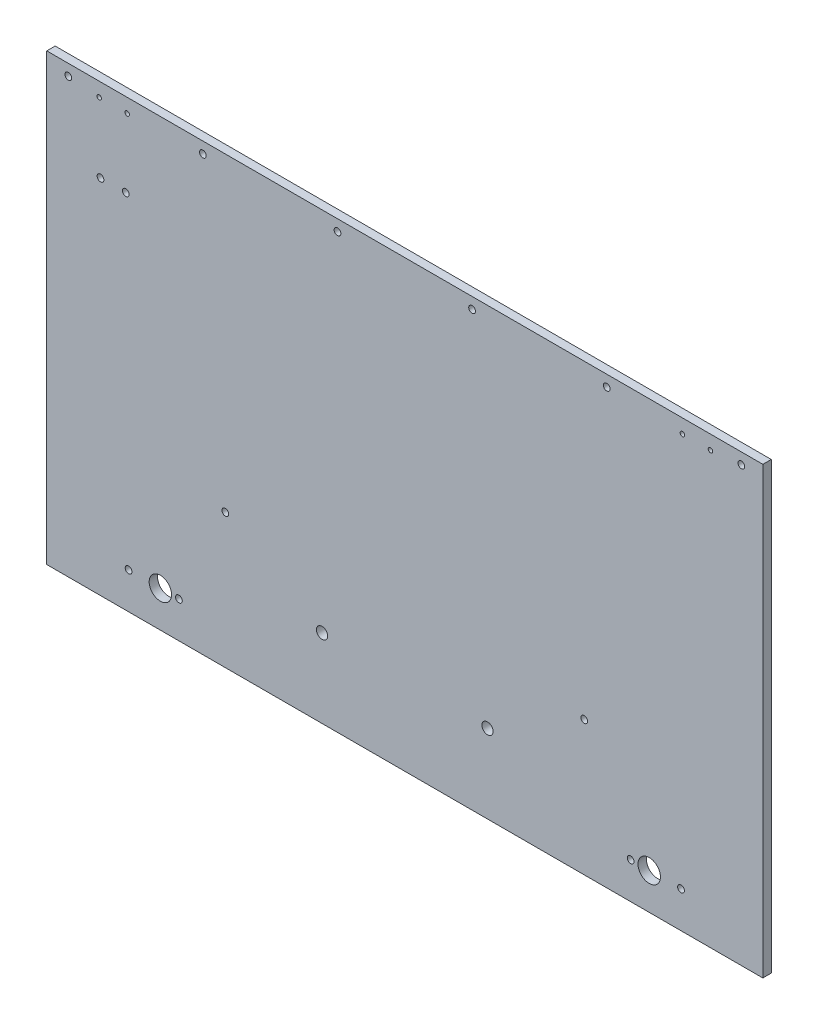
SolidWorks part; units mm, degrees
ref_plane "Front (1)" through (0, 0, 0) normal (0, 0, 1) x (1, 0, 0)
ref_plane "Top (2)" through (0, 0, 0) normal (0, 1, 0) x (1, 0, 0)
ref_plane "Right (3)" through (0, 0, 0) normal (1, 0, 0) x (0, 0, -1)
ref_axis "X-Axis" through (-80.9, 0, 0) along (1, 0, 0)
ref_axis "Y-Axis" through (0, -50, 0) along (0, 1, 0)
ref_axis "Z-Axis" through (0, 0, 50) along (0, 0, -1)
sketch "Sketch1" plane through (0, 0, 0) normal (0, 0, 1) x (1, 0, 0)
  line L1 (0, 0) -> (405.384, 0)
  line L2 (0, 0) -> (0, 251.841)
  line L3 (0, 251.841) -> (405.384, 251.841)
  line L4 (405.384, 0) -> (405.384, 251.841)
  dimension "D1" = 405.384
  dimension "D2" = 251.841
extrude "Boss-Extrude1" add sketch "Sketch1" along normal blind 4.7625
sketch "Sketch2" plane through (0, 0, 4.7625) normal (0, 0, 1) x (1, 0, 0)
  line L0 (46.3255, 20.5486) -> (64.3255, 20.5486) construction
  line L1 (64.3255, 20.5486) -> (74.8243, 20.5486) construction
  line L2 (64.3255, 20.5486) -> (341.0585, 20.5486) construction
  line L4 (29.6545, 243.9035) -> (375.7295, 243.9035) construction
  line L6 (202.692, 20.5486) -> (202.692, 251.841) construction
  line L11 (405.384, 251.841) -> (0, 251.841) construction
  circle A0 centre (29.6545, 243.9035) radius 1.27
  circle A1 centre (45.5295, 243.9035) radius 1.27
  circle A2 centre (359.8545, 243.9035) radius 1.27
  circle A3 centre (375.7295, 243.9035) radius 1.27
  circle A4 centre (64.3255, 20.5486) radius 6.35
  circle A5 centre (341.0585, 20.5486) radius 6.35
  circle A6 centre (46.3255, 20.5486) radius 1.905
  circle A7 centre (74.8243, 20.5486) radius 1.905
  circle A8 centre (330.5597, 20.5486) radius 1.905
  circle A9 centre (359.0585, 20.5486) radius 1.905
  point P16 (202.692, 243.9035)
  dimension "D9" = 2.54
  dimension "D10" = 12.7
  dimension "D6" = 231.2924
  dimension "D7" = 3.81
  dimension "D8" = 3.81
  dimension "D1" = 15.875
  dimension "D2" = 15.875
  dimension "D3" = 314.325
  dimension "D4" = 7.9375
  dimension "D5" = 276.733
extrude "Cut-Extrude1" cut sketch "Sketch2" against normal through all
sketch "Sketch3" plane through (0, 0, 4.7625) normal (0, 0, 1) x (1, 0, 0)
  line L0 (0, 0) -> (405.384, 0) construction
  line L1 (30.4483, 202.836) -> (30.4483, 204.741) construction
  line L2 (155.8607, 44.45) -> (202.692, 0) construction
  line L3 (30.4483, 204.741) -> (30.4483, 206.646) construction
  line L4 (101.092, 76.2) -> (202.692, 0) construction
  line L6 (-5.2705, 269.8285) -> (410.6545, 269.8285) construction
  line L7 (202.692, 0) -> (249.5232, 44.45) construction
  line L8 (0, 251.841) -> (0, 0) construction
  line L9 (405.384, 251.841) -> (0, 251.841) construction
  line L11 (202.692, 0) -> (304.292, 76.2) construction
  line L12 (-0.508, 251.8332) -> (-0.508, 0.0046) construction
  circle A0 centre (44.7358, 204.741) radius 1.905
  circle A1 centre (30.4483, 204.741) radius 1.905
  circle A2 centre (155.8607, 44.45) radius 3.175
  circle A3 centre (249.5232, 44.45) radius 3.175
  circle A4 centre (12.192, 245.491) radius 1.905
  circle A5 centre (88.392, 245.491) radius 1.905
  circle A6 centre (164.592, 245.491) radius 1.905
  circle A7 centre (240.792, 245.491) radius 1.905
  circle A8 centre (316.992, 245.491) radius 1.905
  circle A9 centre (393.192, 245.491) radius 1.905
  circle A10 centre (101.092, 76.2) radius 1.905
  circle A11 centre (304.292, 76.2) radius 1.905
  dimension "D2" = 3.81
  dimension "D7" = 6.35
  dimension "D9" = 3.81
  dimension "D14" = 3.81
  dimension "D1" = 14.2875
  dimension "D4" = 65.0875
  dimension "D5" = 44.45
  dimension "D6" = 93.6625
  dimension "D8" = 30.9562
  dimension "D10" = 12.192
  dimension "D11" = 6.35
  dimension "D13" = 76.2
  dimension "D15" = 203.2
  dimension "D16" = 76.2
  dimension "D12" = 6
extrude "Cut-Extrude2" cut sketch "Sketch3" against normal through all
sketch "Sketch4" plane through (0, 0, 0) normal (0, 0, 1) x (1, 0, 0)
  line L0 (63.5, 6.35) -> (0, 6.35) construction
  line L2 (0, 0) -> (405.384, 0) construction
  text T0 "<b>LCSAP-601</b>"
  dimension "D1" = 63.5
  dimension "D2" = 6.35
extrude "Cut-Extrude3" cut sketch "Sketch4" along normal blind 1.016
